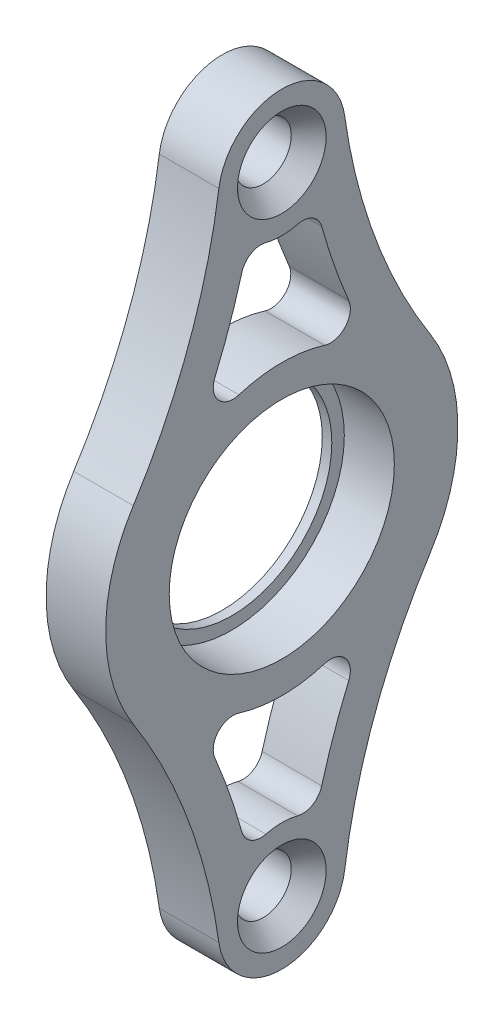
SolidWorks part; units mm, degrees
material "6061-T6 (SS)"
ref_plane "Front Plane" through (0, 0, 0) normal (0, 0, 1) x (1, 0, 0)
ref_plane "Top Plane" through (0, 0, 0) normal (0, 1, 0) x (1, 0, 0)
ref_plane "Right Plane" through (0, 0, 0) normal (1, 0, 0) x (0, 0, -1)
ref_plane "Plane1" through (56.0295, 0, 0) normal (-1, 0, 0) x (0, 0, 1)
sketch "Sketch1" plane through (56.0295, 0, 0) normal (-1, 0, 0) x (0, 0, 1)
  line L0 (-51.1134, 32.5835) -> (-5.0306, 26.107) construction
  line L1 (-23.0873, 0) -> (0, 0) construction
  line L2 (0, 0) -> (0, 25.4) construction
  circle A0 centre (0, -25.4) radius 2.2479 construction
  circle A1 centre (0, 25.4) radius 2.2479 construction
  circle A2 centre (0, -25.4) radius 2.2479
  circle A3 centre (0, 25.4) radius 2.2479
  circle A4 centre (0, 0) radius 9
  circle A5 centre (0, 0) radius 6 construction
  arc A6 (-11.8728, 7.5686) -> (-11.8728, -7.5686) centre (0, 0) ccw
  arc A7 (5.0306, 26.107) -> (-5.0306, 26.107) centre (0, 25.4) ccw
  arc A8 (-5.0306, -26.107) -> (5.0306, -26.107) centre (0, -25.4) ccw
  arc A9 (-5.0306, 26.107) -> (-11.8728, 7.5686) centre (-51.1134, 32.5835) cw
  arc A10 (5.0306, 26.107) -> (11.8728, 7.5686) centre (51.1134, 32.5835) ccw
  arc A11 (5.0306, -26.107) -> (11.8728, -7.5686) centre (51.1134, -32.5835) cw
  arc A12 (-5.0306, -26.107) -> (-11.8728, -7.5686) centre (-51.1134, -32.5835) ccw
  arc A13 (11.8728, -7.5686) -> (11.8728, 7.5686) centre (0, 0) ccw
  dimension "D1" = 18
  dimension "D2" = 12
  dimension "D4" = 10.16
  dimension "D3" = 5.08
  dimension "D5" = 8
extrude "Boss-Extrude1" add sketch "Sketch1" along normal blind 4.7625
sketch "Sketch2" plane through (51.267, 0, 0) normal (-1, 0, 0) x (0, 0, 1)
  arc A0 (-9.1955, 5.8619) -> (-1.8865, 25.6651) centre (-51.1134, 32.5835) ccw
  arc A1 (1.8865, 25.6651) -> (-1.8865, 25.6651) centre (0, 25.4) ccw
  arc A2 (1.8865, 25.6651) -> (9.1955, 5.8619) centre (51.1134, 32.5835) ccw
  arc A3 (9.1955, -5.8619) -> (9.1955, 5.8619) centre (0, 0) ccw
  arc A4 (9.1955, -5.8619) -> (1.8865, -25.6651) centre (51.1134, -32.5835) ccw
  arc A5 (-1.8865, -25.6651) -> (1.8865, -25.6651) centre (0, -25.4) ccw
  arc A6 (-1.8865, -25.6651) -> (-9.1955, -5.8619) centre (-51.1134, -32.5835) ccw
  arc A7 (-9.1955, 5.8619) -> (-9.1955, -5.8619) centre (0, 0) ccw
  arc A8 (-11.8728, 7.5686) -> (-5.0306, 26.107) centre (-51.1134, 32.5835) ccw
  arc A9 (-11.8728, 7.5686) -> (-11.8728, -7.5686) centre (0, 0) ccw
  arc A10 (-5.0306, -26.107) -> (-11.8728, -7.5686) centre (-51.1134, -32.5835) ccw
  arc A11 (-5.0306, -26.107) -> (5.0306, -26.107) centre (0, -25.4) ccw
  arc A12 (11.8728, -7.5686) -> (5.0306, -26.107) centre (51.1134, -32.5835) ccw
  arc A13 (11.8728, -7.5686) -> (11.8728, 7.5686) centre (0, 0) ccw
  arc A14 (5.0306, 26.107) -> (11.8728, 7.5686) centre (51.1134, 32.5835) ccw
  arc A15 (5.0306, 26.107) -> (-5.0306, 26.107) centre (0, 25.4) ccw
  arc A16 (-11.8728, 7.5686) -> (-5.0306, 26.107) centre (-51.1134, 32.5835) ccw construction
  arc A17 (-11.8728, 7.5686) -> (-11.8728, -7.5686) centre (0, 0) ccw construction
  arc A18 (-5.0306, -26.107) -> (-11.8728, -7.5686) centre (-51.1134, -32.5835) ccw construction
  arc A19 (-5.0306, -26.107) -> (5.0306, -26.107) centre (0, -25.4) ccw construction
  arc A20 (11.8728, -7.5686) -> (5.0306, -26.107) centre (51.1134, -32.5835) ccw construction
  arc A21 (11.8728, -7.5686) -> (11.8728, 7.5686) centre (0, 0) ccw construction
  arc A22 (5.0306, 26.107) -> (11.8728, 7.5686) centre (51.1134, 32.5835) ccw construction
  arc A23 (5.0306, 26.107) -> (-5.0306, 26.107) centre (0, 25.4) ccw construction
  circle A24 centre (0, 0) radius 11.54
  circle A25 centre (0, 25.4) radius 5.08
  circle A26 centre (0, -25.4) radius 5.08
  circle A27 centre (0, 0) radius 9 construction
  dimension "D3" = 2.54
  dimension "D1" = 0
  dimension "D2" = 3.175
extrude "Cut-Extrude1" cut sketch "Sketch2" against normal through all contours A25 A0 A24 A2 | A26 A4 A24 A6 region at (51.267, 15.0199, 0) region at (51.267, -15.0199, 0)
fillet "Fillet1" radius 1.5875 8 edges at (53.6483, 8.8063, 7.4579) (53.6483, 8.8063, -7.4579) (53.6483, 21.1234, 2.7417) (53.6483, -8.8063, -7.4579) (53.6483, -8.8063, 7.4579) (53.6483, -21.1234, 2.7417) (53.6483, -21.1234, -2.7417) (53.6483, 21.1234, -2.7417)
sketch "Sketch5" plane through (56.0295, 0, 0) normal (-1, 0, 0) x (0, 0, 1)
  point P0 (0, 25.4)
  point P3 (0, -25.4)
hole_wizard "CSK for #6 Flat Head Machine Screw1" positions "Sketch5" profile "Sketch4" countersink size "#6" standard "ANSI Inch"
sketch "Sketch4" plane through (56.0295, 25.4, 0) normal (0, 1, 0) x (0, 0, -1)
  line L0 (0, 0) -> (0, 7.6434)
  line L1 (0, 7.6434) -> (2.1526, 6.35)
  line L2 (2.1526, 6.35) -> (2.1526, 1.5998)
  line L3 (2.1526, 1.5998) -> (3.5433, 0)
  line L5 (3.5433, 0) -> (0, 0)
  line L6 (-2.1526, 1.5998) -> (-3.5433, 0) construction
  line L10 (0, 7.6434) -> (-2.1526, 6.35) construction
  line L11 (0, -6.35) -> (0, 107.95) construction
  dimension "Hole Dia." = 4.3053
  dimension "Hole Depth" = 6.35
  dimension "Near C'Sink Dia." = 7.0866
  dimension "Near C'Sink Angle" = 82
  dimension "Drill Angle" = 118
sketch "Sketch6" plane through (56.0295, 0, 0) normal (1, 0, 0) x (0, 0, -1)
  circle A0 centre (0, 0) radius 9 construction
  circle A1 centre (0, 0) radius 9
  circle A2 centre (0, 0) radius 8
  dimension "D1" = 1
extrude "Boss-Extrude2" add sketch "Sketch6" along normal offset from surface (0.7625 mm away) 4 from surface up to face at (56.0295, 25.4, -3.5433) starting at face at (51.267, -15.9859, 0)
equation "\"D1@Sketch1\"=18mm"
equation "\"D2@Sketch1\"=12mm"
equation "\"D1@Boss-Extrude2\"=4mm"
